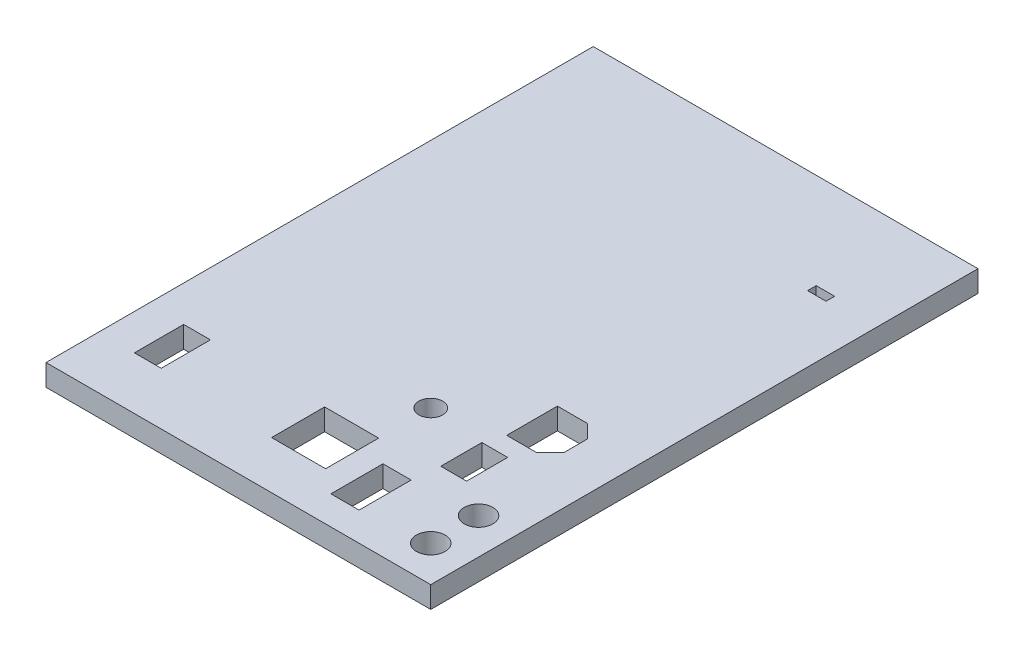
SolidWorks part; units mm, degrees
material "Perspex (TM) GS Acrylic Cast Sheet"
ref_plane "Front Plane" through (0, 0, 0) normal (0, 0, 1) x (1, 0, 0)
ref_plane "Top Plane" through (0, 0, 0) normal (0, 1, 0) x (1, 0, 0)
ref_plane "Right Plane" through (0, 0, 0) normal (1, 0, 0) x (0, 0, -1)
sketch "Sketch1" plane through (0, 0, 0) normal (0, 1, 0) x (1, 0, 0)
  line L1 (-80.5, -114.5) -> (80.5, -114.5)
  line L2 (-80.5, -114.5) -> (-80.5, 114.5)
  line L3 (-80.5, 114.5) -> (80.5, 114.5)
  line L4 (80.5, -114.5) -> (80.5, 114.5)
  line L5 (-80.5, -114.5) -> (80.5, 114.5) construction
  line L6 (-80.5, 114.5) -> (80.5, -114.5) construction
  point P0 (0, 0)
  dimension "D1" = 161
  dimension "D2" = 229
extrude "Boss-Extrude1" add sketch "Sketch1" along normal blind 9
sketch "Sketch2" plane through (0, 9, 0) normal (0, 1, 0) x (1, 0, 0)
  line L0 (65.5, -79.5) -> (65.5, -99.5) construction
  line L1 (80.5, -114.5) -> (80.5, 114.5) construction
  line L2 (38.5, -102.5) -> (26.7, -102.5)
  line L3 (38.5, -102.5) -> (38.5, -80.7)
  line L4 (38.5, -80.7) -> (26.7, -80.7)
  line L5 (26.7, -102.5) -> (26.7, -80.7)
  line L6 (-80.5, -114.5) -> (80.5, -114.5) construction
  line L7 (-80.5, 114.5) -> (-80.5, -114.5) construction
  line L8 (16.5, -94.5) -> (-6.1, -94.5)
  line L9 (16.5, -94.5) -> (16.5, -72.3)
  line L10 (16.5, -72.3) -> (-6.1, -72.3)
  line L11 (-6.1, -94.5) -> (-6.1, -72.3)
  line L12 (-54.3, -92.5) -> (-65.5, -92.5)
  line L13 (-54.3, -92.5) -> (-54.3, -71.9)
  line L14 (-54.3, -71.9) -> (-65.5, -71.9)
  line L15 (-65.5, -92.5) -> (-65.5, -71.9)
  line L16 (80.5, 114.5) -> (-80.5, 114.5) construction
  line L17 (42.3, -23.3) -> (54.9, -23.3)
  line L18 (42.3, -23.3) -> (42.3, -44.5)
  line L19 (42.3, -44.5) -> (54.9, -44.5)
  line L21 (52.8, 74.5) -> (60.5, 74.5)
  line L22 (52.8, 74.5) -> (52.8, 70.9)
  line L23 (52.8, 70.9) -> (60.5, 70.9)
  line L24 (60.5, 74.5) -> (60.5, 70.9)
  line L25 (54.9, -44.5) -> (60.5, -38.9)
  line L26 (60.5, -38.9) -> (60.5, -28.9)
  line L27 (60.5, -28.9) -> (54.9, -23.3)
  line L29 (39.7, -69.5) -> (50.5, -69.5)
  line L30 (39.7, -69.5) -> (39.7, -52.3)
  line L31 (39.7, -52.3) -> (50.5, -52.3)
  line L32 (50.5, -69.5) -> (50.5, -52.3)
  line L33 (39.7, -69.5) -> (50.5, -52.3) construction
  line L34 (39.7, -52.3) -> (50.5, -69.5) construction
  circle A0 centre (16.5, -50.5) radius 5
  circle A1 centre (65.5, -99.5) radius 6
  circle A2 centre (65.5, -79.5) radius 6
  point P38 (45.1, -60.9)
  dimension "D19" = 12
  dimension "D27" = 10
  dimension "D1" = 42
  dimension "D2" = 12
  dimension "D3" = 20
  dimension "D4" = 64
  dimension "D5" = 15
  dimension "D6" = 22
  dimension "D7" = 64
  dimension "D8" = 64
  dimension "D9" = 135
  dimension "D10" = 70
  dimension "D11" = 40
  dimension "D12" = 20
  dimension "D13" = 7.7
  dimension "D14" = 3.6
  dimension "D15" = 20
  dimension "D16" = 18.2
  dimension "D17" = 21.2
  dimension "D18" = 10
  dimension "D20" = 20
  dimension "D21" = 15
  dimension "D22" = 15
  dimension "D23" = 30
  dimension "D24" = 45
  dimension "D25" = 10.8
  dimension "D26" = 17.2
  dimension "D28" = 11.8
  dimension "D29" = 21.8
  dimension "D30" = 22.2
  dimension "D31" = 22.6
  dimension "D32" = 11.2
  dimension "D33" = 20.6
extrude "Cut-Extrude1" cut sketch "Sketch2" against normal through all
equation "\"PCLength\"= 143mm'Length across I/O from PS to GPU"
equation "\"PCWidth\"= 340mm'Distance of longest part parallel to GPU(ussually GPU)"
equation "\"PCHeight\"= 190mm'Tallest point with mobo laying flat"
equation "\"WallThickness\"= 9mm'Thickness of each outer tank wall"
equation "\"ThermoBarrierThickness\"= 6mm'Thickness of barrier between hot side and cold side"
equation "\"HotSideGap\"= 15mm'Space in the hot side that hot fluid flows into"
equation "\"PCClearance\"= 40mm'Clearance from top of tank to top of PC"
equation "\"RadiatorHeight\"= 277.37mm'Final Height from ground of radiators"
equation "\"AirflowGap\"= 26mm'Distance between radiators and tank for airflow"
equation "\"VolumeSubtraction\"= 230mm"
equation "\"D1@Sketch1\"=\"PCLength\" + (2 * \"WallThickness\")"
equation "\"D1@Boss-Extrude1\"=\"WallThickness\""
equation "\"D2@Sketch1\"=\"PCHeight\" + \"ThermoBarrierThickness\" + \"HotSideGap\" + (2 * \"WallThickness\")"
